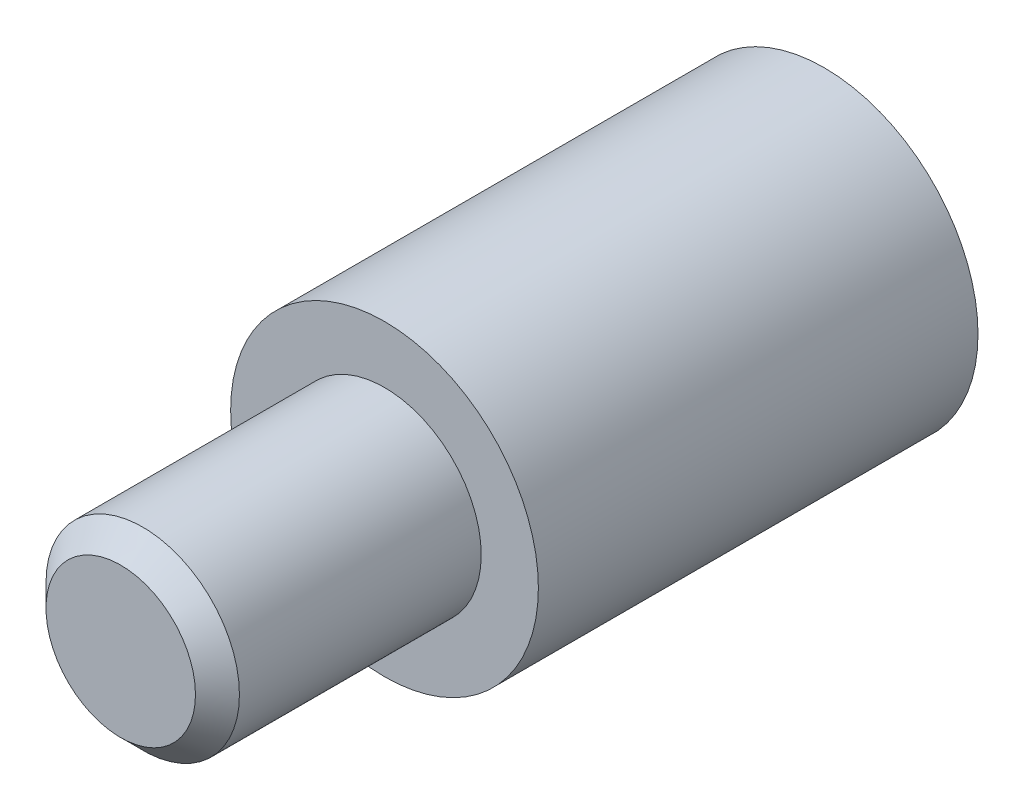
SolidWorks part; units mm, degrees
ref_plane "Front Plane" through (0, 0, 0) normal (0, 0, 1) x (1, 0, 0)
ref_plane "Top Plane" through (0, 0, 0) normal (0, 1, 0) x (1, 0, 0)
ref_plane "Right Plane" through (0, 0, 0) normal (1, 0, 0) x (0, 0, -1)
sketch "Sketch1" plane through (0, 0, 106.9354) normal (0, 0, -1) x (-1, 0, 0)
  circle A0 centre (-59.7974, 58.0158) radius 3.5
  dimension "D1" = 7
extrude "Boss-Extrude1" add sketch "Sketch1" along normal blind 7
sketch "Sketch2" plane through (0, 0, 99.9354) normal (0, 0, -1) x (-1, 0, 0)
  circle A0 centre (-59.7974, 58.0158) radius 3.5
  circle A1 centre (-59.7974, 58.0158) radius 2
  dimension "D1" = 4
extrude "Boss-Extrude2" add sketch "Sketch2" along normal blind 3
sketch "Sketch3" plane through (0, 0, 106.9354) normal (0, 0, 1) x (1, 0, 0)
  circle A0 centre (59.7974, 58.0158) radius 2.2
  circle A1 centre (59.7974, 58.0158) radius 2.5 construction
  dimension "D1" = 0.3
extrude "Boss-Extrude3" add sketch "Sketch3" along normal blind 6
chamfer "Chamfer1" distance 0.5 angle 45 1 edges at (61.9974, 58.0158, 112.9354)
